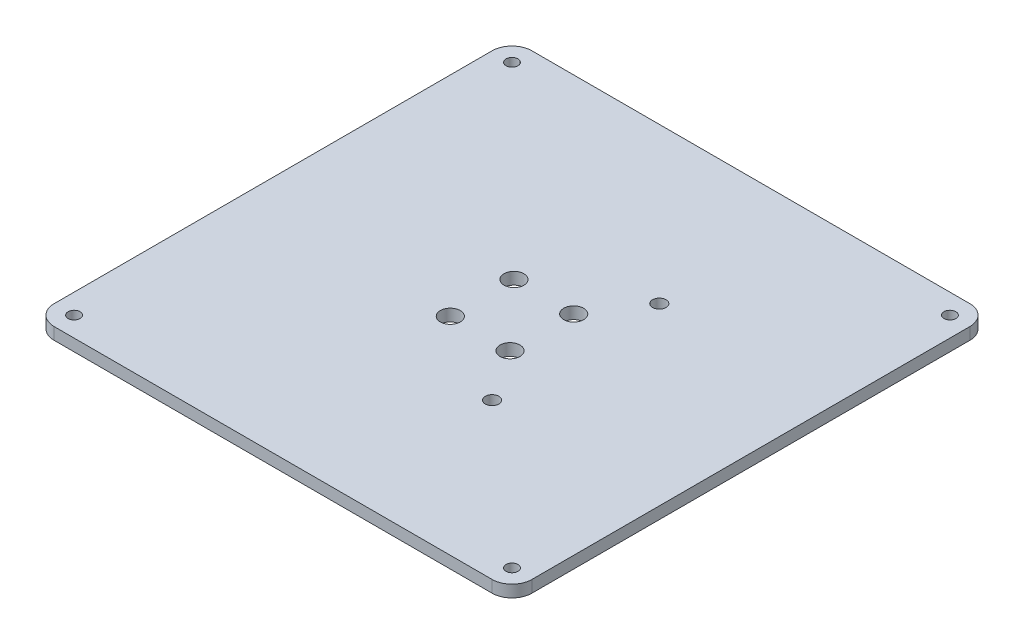
SolidWorks part; units mm, degrees
ref_plane "Alzado" through (0, 0, 0) normal (0, 0, 1) x (1, 0, 0)
ref_plane "Planta" through (0, 0, 0) normal (0, 1, 0) x (1, 0, 0)
ref_plane "Vista lateral" through (0, 0, 0) normal (1, 0, 0) x (0, 0, -1)
sketch "Sketch1" plane through (0, 0, 0) normal (0, 1, 0) x (1, 0, 0)
  line L1 (-7.5, -8) -> (7.5, -8) construction
  line L2 (-7.5, -8) -> (-7.5, 8) construction
  line L3 (-7.5, 8) -> (7.5, 8) construction
  line L4 (7.5, -8) -> (7.5, 8) construction
  line L5 (-7.5, -8) -> (7.5, 8) construction
  line L6 (-7.5, 8) -> (7.5, -8) construction
  line L7 (-60, -60) -> (60, -60)
  line L8 (-60, -60) -> (-60, 60)
  line L9 (-60, 60) -> (60, 60)
  line L10 (60, -60) -> (60, 60)
  circle A0 centre (-7.5, -8) radius 2.5
  circle A1 centre (7.5, 8) radius 2.5
  circle A2 centre (7.5, -8) radius 2.5
  circle A3 centre (-7.5, 8) radius 2.5
  point P0 (0, 0)
  point P10 (0, 0)
  point P16 (-60, 0)
  point P17 (0, -60)
  dimension "D3" = 5
  dimension "D1" = 16
  dimension "D2" = 15
  dimension "D4" = 120
  dimension "D5" = 120
extrude "Boss-Extrude1" add sketch "Sketch1" along normal blind 3
fillet "Fillet1" radius 5 4 edges at (-60, 1.5, -60) (60, 1.5, -60) (60, 1.5, 60) (-60, 1.5, 60)
sketch "Sketch2" plane through (0, 3, 0) normal (0, 1, 0) x (1, 0, 0)
  line L0 (-55, 55) -> (-55, 60) construction
  line L1 (-55, 55) -> (-60, 55) construction
  circle A0 centre (-55, 55) radius 1.5
  dimension "D1" = 3
extrude "Cut-Extrude1" cut sketch "Sketch2" against normal through all
mirror "Mirror3" about plane through (0, 0, 0) normal (0, 0, 1) of "Cut-Extrude1" second plane through (0, 0, 0) second plane normal (1, 0, 0)
sketch "Sketch3" plane through (0, 3, 0) normal (0, 1, 0) x (1, 0, 0)
  line L0 (16, 21) -> (16, -21) construction
  circle A2 centre (16, 21) radius 1.7
  circle A3 centre (16, -21) radius 1.7
  point P4 (16, 0)
  dimension "D2" = 42
  dimension "D1" = 3.4
  dimension "D3" = 16
extrude "Cut-Extrude2" cut sketch "Sketch3" against normal through all
